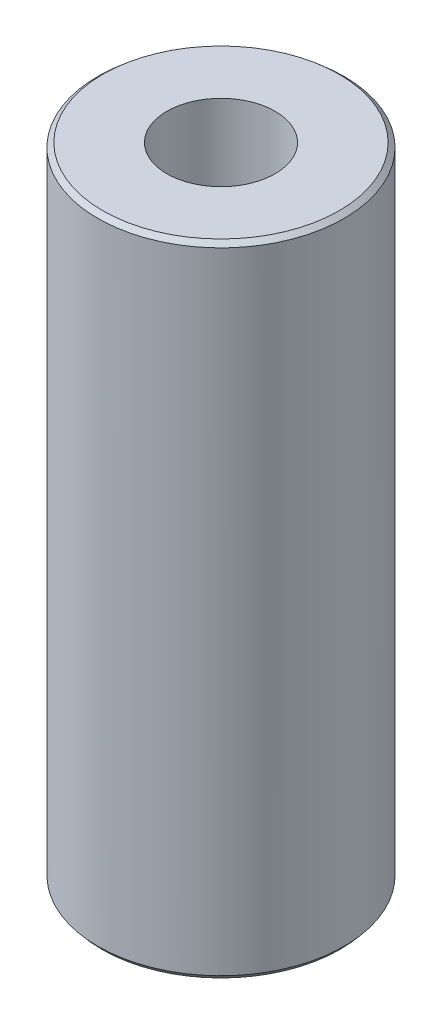
SolidWorks part; units mm, degrees
ref_plane "Front Plane" through (0, 0, 0) normal (0, 0, 1) x (1, 0, 0)
ref_plane "Top Plane" through (0, 0, 0) normal (0, 1, 0) x (1, 0, 0)
ref_plane "Right Plane" through (0, 0, 0) normal (1, 0, 0) x (0, 0, -1)
sketch "Sketch1" plane through (0, 0, 0) normal (0, 1, 0) x (1, 0, 0)
  circle A0 centre (0, 0) radius 40
  dimension "SHAFT_OD" = 80
extrude "Boss-Extrude1" add sketch "Sketch1" along normal blind 207.8
sketch "Sketch2" plane through (0, 0, 0) normal (0, 1, 0) x (1, 0, 0)
  circle A0 centre (0, 0) radius 17.6006
  dimension "BORE_D" = 35.2012
extrude "Cut-Extrude1" cut sketch "Sketch2" along normal through all
chamfer "Chamfer1" distance 1.3757 angle 49.235 2 edges at (0, 207.8, 40) (0, 0, 40) first distance on face at (0, 207.8, 40) first distance on face at (0, 0, 17.6006)
